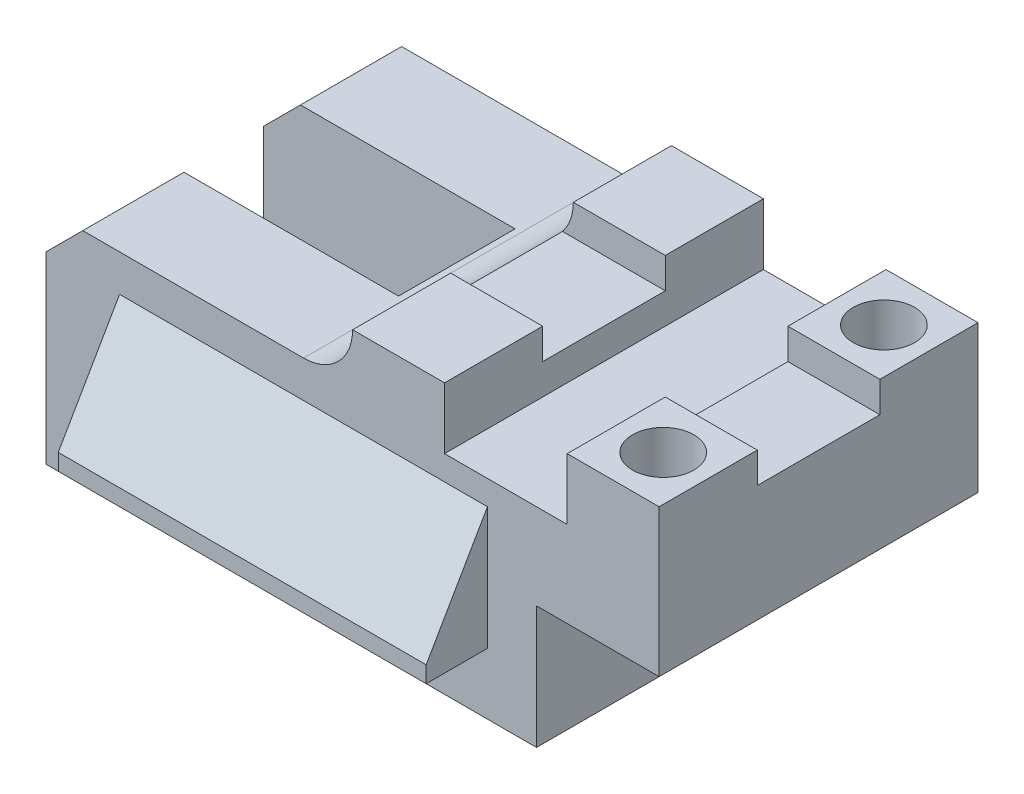
SolidWorks part; units mm, degrees
ref_plane "Plano frontal" through (0, 0, 0) normal (0, 0, 1) x (1, 0, 0)
ref_plane "Plano superior" through (0, 0, 0) normal (0, 1, 0) x (1, 0, 0)
ref_plane "Plano direito" through (0, 0, 0) normal (1, 0, 0) x (0, 0, -1)
sketch "Esboço2" plane through (0, 0, 0) normal (0, 1, 0) x (1, 0, 0)
  line L0 (-50, 9.5) -> (-9, 9.5)
  line L1 (-50, 26) -> (50, 26)
  line L2 (-50, 26) -> (-50, -26)
  line L3 (-50, -26) -> (50, -26)
  line L4 (50, 26) -> (50, -26)
  line L5 (-50, 26) -> (50, -26) construction
  line L6 (-50, -26) -> (50, 26) construction
  line L7 (-9, 9.5) -> (-9, -9.5)
  line L8 (-9, -9.5) -> (-50, -9.5)
  point P0 (0, 0)
  point P10 (-11.9708, 12.3611)
  point P11 (-11.9708, 13.5322)
  dimension "D1" = 100
  dimension "D2" = 52
  dimension "D3" = 41
  dimension "D4" = 19
  dimension "D5" = 16.5
extrude "Ressalto-extrusão2" add sketch "Esboço2" along normal blind 44 contours L7 L8 L2 L3 L4 L1 L0 region at (5.198, 0, 0)
sketch "Esboço4" plane through (0, 44, 0) normal (0, 1, 0) x (1, 0, 0)
  line L0 (50, 10) -> (35, 10)
  line L1 (50, 26) -> (50, -26) construction
  line L2 (35, 10) -> (35, -10)
  line L3 (35, -10) -> (50, -10)
  line L4 (50, -10) -> (50, 10)
  line L5 (-50, 26) -> (50, 26) construction
  line L6 (35, 26) -> (15, 26)
  line L7 (15, 26) -> (15, -26)
  line L8 (35, -10) -> (35, -26)
  line L9 (-50, -26) -> (50, -26) construction
  line L10 (15, 10) -> (0, 10)
  line L11 (0, 10) -> (0, -10)
  line L12 (35, 10) -> (35, 26)
  line L13 (0, -10) -> (15, -10)
  line L14 (0, 10) -> (0, 26)
  line L15 (15, -26) -> (35, -26)
  line L16 (0, 26) -> (15, 26)
  line L17 (15, 26) -> (15, 10)
  line L18 (0, -10) -> (0, -26)
  line L19 (0, -26) -> (15, -26)
  line M4 (-9, 9.5) -> (-9, -9.5)
  line M5 (-9, -9.5) -> (-50, -9.5)
  line M6 (-50, -9.5) -> (-50, -26)
  line M7 (-50, -26) -> (50, -26)
  line M8 (50, -26) -> (50, 26)
  line M9 (50, 26) -> (-50, 26)
  line M10 (-50, 26) -> (-50, 9.5)
  line M11 (-50, 9.5) -> (-9, 9.5)
  dimension "D1" = 20
  dimension "D2" = 15
  dimension "D3" = 20
  dimension "D4" = 16
  dimension "D5" = 20
extrude "Corte-extrusão2" cut sketch "Esboço4" against normal blind 5 contours L2 L3 L0 M8 region at (42.5, 44, 0)
extrude "Corte-extrusão4" cut sketch "Esboço4<4>" against normal blind 10 contours L2 L12 L7 L8 M9 M7 region at (25, 44, 0)
sketch "Esboço4<4>" plane through (0, 44, 0) normal (0, 1, 0) x (1, 0, 0) same geometry as "Esboço4"
extrude "Corte-extrusão5" cut sketch "Esboço4<5>" against normal blind 5 contours L11 L13 L7 L10 region at (7.5, 44, 0)
sketch "Esboço4<5>" plane through (0, 44, 0) normal (0, 1, 0) x (1, 0, 0) same geometry as "Esboço4"
extrude "Corte-extrusão6" cut sketch "Esboço4<6>" against normal blind 8 contours L18 L11 L14 M9 M10 M11 M4 M5 M6 M7 region at (-0.7214, 44, -18)
sketch "Esboço4<6>" plane through (0, 44, 0) normal (0, 1, 0) x (1, 0, 0) same geometry as "Esboço4"
chamfer "Chanfro2" distance 6 angle 45 2 edges at (-50, 36, 17.75) (-50, 36, -17.75)
fillet "Filete1" radius 8 1 edges at (0, 36, 0)
sketch "Esboço5" plane through (0, 44, 0) normal (0, 1, 0) x (1, 0, 0)
  line L0 (35, 26) -> (50, 26) construction
  line L1 (35, -26) -> (50, -26) construction
  circle A0 centre (42.6567, 18) radius 5
  circle A1 centre (42.6567, -18) radius 5
  point P4 (0, 0)
  point P5 (0, 0)
  dimension "D1" = 10
  dimension "D2" = 10
  dimension "D3" = 8
  dimension "D4" = 8
extrude "Corte-extrusão7" cut sketch "Esboço5" against normal through all
sketch "Esboço6" plane through (0, 0, 26) normal (0, 0, 1) x (1, 0, 0)
  line L5 (50, 0) -> (30, 0)
  line L6 (50, 0) -> (50, 20)
  line L7 (50, 20) -> (30, 20)
  line L8 (30, 0) -> (30, 20)
  dimension "D1" = 20
  dimension "D2" = 20
extrude "Corte-extrusão8" cut sketch "Esboço6" against normal through all
sketch "Esboço7" plane through (0, 0, 26) normal (0, 0, 1) x (1, 0, 0)
  line L0 (-38, 10) -> (22, 10)
  line L1 (-38, 30) -> (-38, 10)
  line L2 (-50, 0) -> (30, 0) construction
  line L3 (22, 10) -> (22, 30)
  line L4 (22, 30) -> (-38, 30)
  dimension "D1" = 20
  dimension "D2" = 60
  dimension "D3" = 10
extrude "Ressalto-extrusão3" add sketch "Esboço7" along normal blind 10
chamfer "Chanfro5" distance 10 angle 60 1 edges at (-8, 30, 36) first distance on face at (-8, 30, 31)
